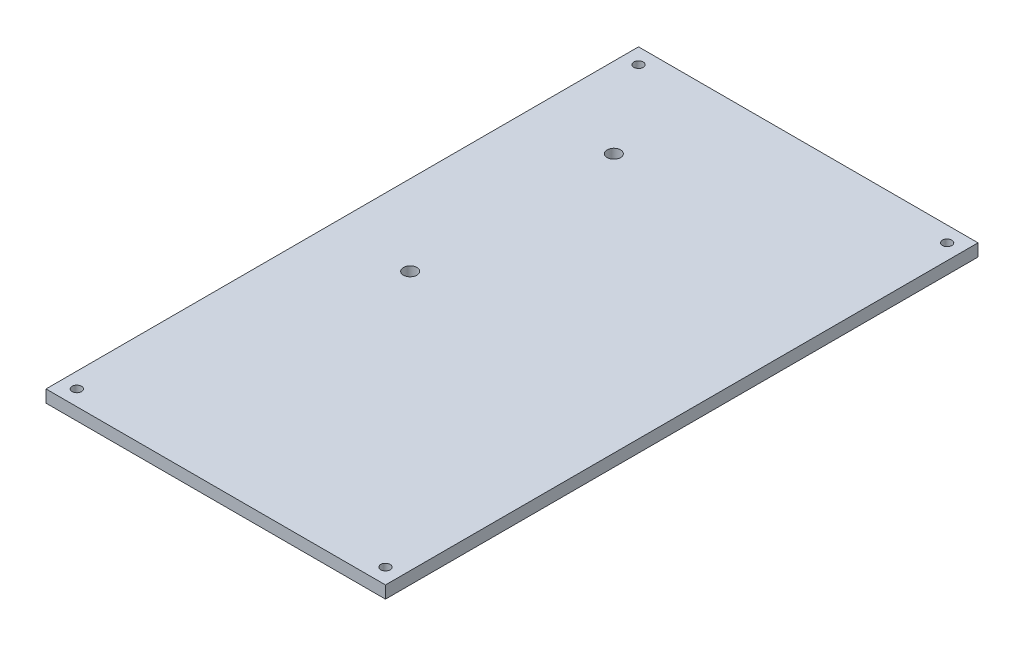
SolidWorks part; units mm, degrees
material "PCB (FR-4) (Recolor)"
ref_plane "Front Plane" through (0, 0, 0) normal (0, 0, 1) x (1, 0, 0)
ref_plane "Top Plane" through (0, 0, 0) normal (0, 1, 0) x (1, 0, 0)
ref_plane "Right Plane" through (0, 0, 0) normal (1, 0, 0) x (0, 0, -1)
sketch "Sketch2" plane through (0, 0, 0) normal (0, 1, 0) x (1, 0, 0)
  line L1 (0, 0) -> (55, 0)
  line L2 (0, 0) -> (0, 96)
  line L3 (0, 96) -> (55, 96)
  line L4 (55, 0) -> (55, 96)
  dimension "D1" = 96
  dimension "D2" = 55
extrude "Boss-Extrude1" add sketch "Sketch2" along normal blind 2
sketch "Sketch3" plane through (0, 2, 0) normal (0, 1, 0) x (1, 0, 0)
  line L0 (2.5, 2.5) -> (52.5, 2.5) construction
  line L1 (52.5, 2.5) -> (52.5, 93.5) construction
  line L2 (0, 0) -> (55, 0) construction
  line L3 (55, 0) -> (55, 96) construction
  line L4 (0, 96) -> (0, 0) construction
  line L5 (55, 96) -> (0, 96) construction
  line L6 (2.5, 93.5) -> (52.5, 93.5) construction
  line L9 (2.5, 93.5) -> (2.5, 2.5) construction
  circle A0 centre (2.5, 2.5) radius 0.762
  circle A1 centre (52.5, 2.5) radius 0.762
  circle A2 centre (52.5, 93.5) radius 0.762
  circle A3 centre (2.5, 93.5) radius 0.762
  dimension "D1" = 1.524
  dimension "D2" = 2.5
  dimension "D3" = 2.5
  dimension "D4" = 2.5
  dimension "D5" = 2.5
extrude "Cut-Extrude1" cut sketch "Sketch3" against normal through all
sketch "Sketch4" plane through (0, 2, 0) normal (0, 1, 0) x (1, 0, 0)
  line L0 (55, 96) -> (0, 96) construction
  line L3 (0, 0) -> (55, 0) construction
  line L7 (0, 96) -> (0, 0) construction
  line L10 (55, 0) -> (55, 96) construction
  line L19 (55, 48) -> (0, 48) construction
  line L20 (5, 91) -> (5, 96) construction
  line L21 (5, 91) -> (0, 91) construction
  line L22 (50, 91) -> (50, 84) construction
  line L23 (21, 84) -> (50, 84) construction
  line L24 (21, 11) -> (21, 84) construction
  line L25 (5, 11) -> (21, 11) construction
  line L26 (5, 91) -> (5, 0) construction
  line L27 (13, 11) -> (13, 96) construction
  line L28 (50, 91) -> (5, 91) construction
  line L29 (5, 94) -> (50, 94) construction
  line L30 (50, 91) -> (50, 96) construction
  line L31 (50, 91) -> (55, 91) construction
  point P0 (50.0956, 94)
  point P23 (13, 79)
  point P27 (13, 46)
  dimension "D1" = 16
  dimension "D2" = 45
  dimension "D3" = 83
  dimension "D4" = 10
  dimension "D5" = 35
  dimension "D6" = 15
  dimension "D7" = 2
hole_wizard "#44 (0.086) Diameter Hole2" positions "Sketch8" profile "Sketch9" hole size "#44" standard "ANSI Inch" end condition through all
sketch "Sketch8" plane through (0, 2, 0) normal (0, 1, 0) x (1, 0, 0)
  point P0 (13, 79)
  point P3 (13, 46)
sketch "Sketch9" plane through (13, 2, -79) normal (1, 0, 0) x (0, 0, 1)
  line L0 (0, 0) -> (0, 2)
  line L1 (0, 2) -> (1.0922, 2)
  line L2 (1.0922, 2) -> (1.0922, 0)
  line L5 (1.0922, 0) -> (0, 0)
  line L11 (0, -6.35) -> (0, 107.95) construction
  dimension "Thru Hole Dia." = 2.1844
  dimension "Thru Hole Depth" = 2
